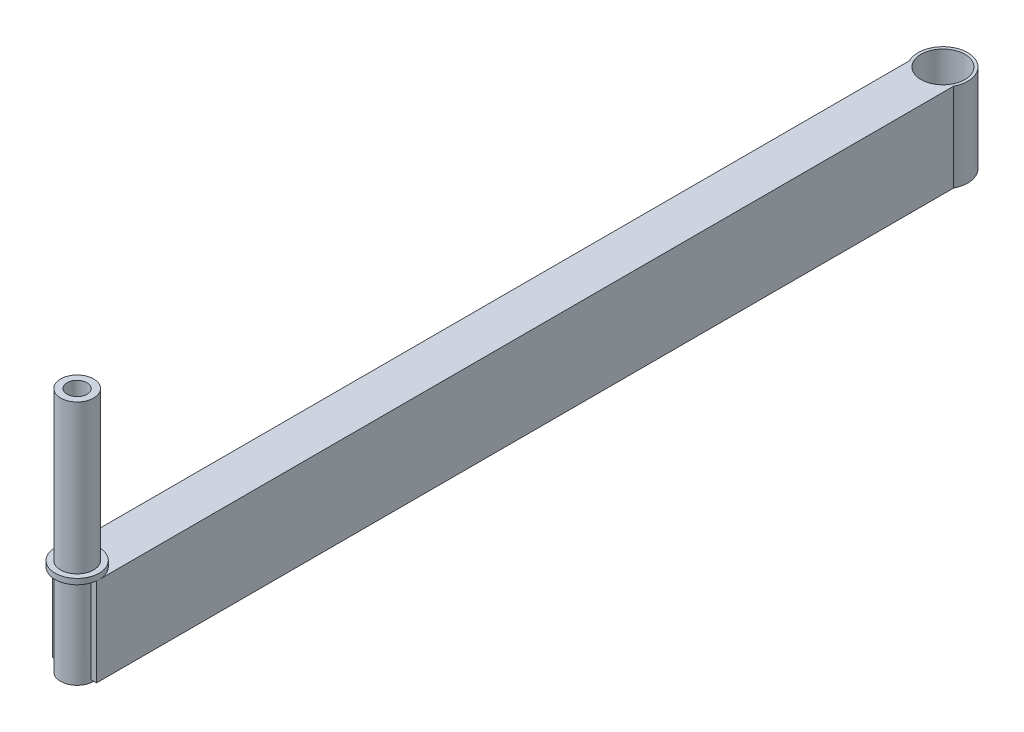
SolidWorks part; units mm, degrees
material "6061-T6 (SS)"
ref_plane "Front Plane" through (0, 0, 0) normal (0, 0, 1) x (1, 0, 0)
ref_plane "Top Plane" through (0, 0, 0) normal (0, 1, 0) x (1, 0, 0)
ref_plane "Right Plane" through (0, 0, 0) normal (1, 0, 0) x (0, 0, -1)
sketch "Sketch1" plane through (0, 0, 0) normal (0, 0, 1) x (1, 0, 0)
  line L0 (-11.1252, -23.8252) -> (-11.1252, 23.8252)
  line L1 (-12.7, -25.4) -> (12.7, -25.4)
  line L2 (-12.7, -25.4) -> (-12.7, 25.4)
  line L3 (-12.7, 25.4) -> (12.7, 25.4)
  line L4 (12.7, -25.4) -> (12.7, 25.4)
  line L5 (-12.7, -25.4) -> (12.7, 25.4) construction
  line L6 (-12.7, 25.4) -> (12.7, -25.4) construction
  line L7 (-11.1252, 23.8252) -> (11.1252, 23.8252)
  line L8 (11.1252, -23.8252) -> (11.1252, 23.8252)
  line L9 (-11.1252, -23.8252) -> (11.1252, -23.8252)
  point P0 (0, 0)
  dimension "D1" = 25.4
  dimension "D2" = 50.8
  dimension "D3" = 1.5748
extrude "Boss-Extrude1" add sketch "Sketch1" along normal blind 498.475
sketch "Sketch2" plane through (0, 25.4, 0) normal (0, 1, 0) x (1, 0, 0)
  line L0 (12.7, -498.475) -> (-12.7, -498.475) construction
  line L1 (12.7, -8.9803) -> (11.1125, -8.9803) construction
  line L2 (12.7, -498.475) -> (12.7, 0) construction
  circle A0 centre (0, 0) radius 14.2875
  circle A1 centre (0, -498.475) radius 9.525
  dimension "D1" = 28.575
  dimension "D2" = 19.05
  dimension "D3" = 1.5875
  dimension "D4" = 489.4947
extrude "Cut-Extrude1" cut sketch "Sketch2" against normal through all
sketch "Sketch3" plane through (0, 25.4, 0) normal (0, 1, 0) x (1, 0, 0)
  circle A0 centre (0, 0) radius 14.2875
  circle A1 centre (0, 0) radius 12.6365
  dimension "D1" = 28.575
  dimension "D2" = 1.651
extrude "Boss-Extrude2" add sketch "Sketch3" against normal blind 50.8
sketch "Sketch4" plane through (0, 25.4, 0) normal (0, 1, 0) x (1, 0, 0)
  circle A0 centre (0, -498.475) radius 9.525
  circle A1 centre (0, -498.475) radius 6.35
  dimension "D1" = 19.05
  dimension "D2" = 3.175
extrude "Boss-Extrude3" add sketch "Sketch4" along normal blind 88.9 and the other way blind 52.3875
sketch "Sketch5" plane through (0, 25.4, 0) normal (0, 1, 0) x (1, 0, 0)
  circle A0 centre (0, -498.475) radius 12.7
  circle A1 centre (0, -498.475) radius 9.525
  dimension "D1" = 25.4
  dimension "D2" = 19.05
extrude "Boss-Extrude4" add sketch "Sketch5" along normal blind 3.175
sketch "Sketch6" plane through (0, 114.3, 0) normal (0, 1, 0) x (1, 0, 0)
  circle A0 centre (0, -498.475) radius 6.35
extrude "Boss-Extrude5" add sketch "Sketch6" against normal blind 19.05
hole_wizard "Tap Drill for 1/2-20 Tap1" positions "Sketch8" profile "Sketch7" hole size "1/2-20" standard "ANSI Inch" end condition up to next
sketch "Sketch8" plane through (0, 114.3, 0) normal (0, 1, 0) x (1, 0, 0)
  point P0 (0, -498.475)
sketch "Sketch7" plane through (0, 114.3, 498.475) normal (1, 0, 0) x (0, 0, 1)
  line L0 (0, 0) -> (0, 19.05)
  line L1 (0, 19.05) -> (5.7544, 19.05)
  line L2 (5.7544, 19.05) -> (5.7544, 0)
  line L5 (5.7544, 0) -> (0, 0)
  line L11 (0, -6.35) -> (0, 107.95) construction
  dimension "Thru Hole Dia." = 11.5087
  dimension "Thru Hole Depth" = 19.05
sketch "Sketch9" plane through (12.7, 0, 0) normal (1, 0, 0) x (0, 0, -1)
  line L1 (-498.475, 25.4) -> (-499.999, 25.4)
  line L2 (-498.475, 25.4) -> (-498.475, -25.4)
  line L3 (-498.475, -25.4) -> (-499.999, -25.4)
  line L4 (-499.999, 25.4) -> (-499.999, -25.4)
  dimension "D1" = 50.8
  dimension "D2" = 1.524
extrude "Boss-Extrude6" add sketch "Sketch9" against normal up to surface (3.175 mm away) up to face at (0, -24.6126, 493.7125)
sketch "Sketch10" plane through (-12.7, 0, 0) normal (-1, 0, 0) x (0, 0, 1)
  line L1 (498.475, 25.4) -> (499.999, 25.4)
  line L2 (498.475, 25.4) -> (498.475, -25.4)
  line L3 (498.475, -25.4) -> (499.999, -25.4)
  line L4 (499.999, 25.4) -> (499.999, -25.4)
  dimension "D1" = 1.524
extrude "Boss-Extrude7" add sketch "Sketch10" against normal up to surface (3.2977 mm away) up to face at (-0.0153, 0, 496.2842)
sketch "Sketch11" plane through (0, 25.4, 0) normal (0, 1, 0) x (1, 0, 0)
  line L0 (0, 0) -> (0, -191.4003) construction
  line L1 (12.7, -498.475) -> (12.7, -6.5454) construction
  line L2 (12.7, -58.7375) -> (15.0812, -58.7375)
  line L3 (12.7, -58.7375) -> (12.7, -39.6875)
  line L4 (12.7, -39.6875) -> (15.0812, -39.6875)
  line L5 (15.0812, -58.7375) -> (15.0812, -39.6875)
  dimension "D1" = 39.6875
  dimension "D2" = 19.05
  dimension "D3" = 2.3813
extrude "Boss-Extrude8" [suppressed] add sketch "Sketch11" along normal blind 42.5577 and the other way blind 38.1
sketch "Sketch12" [suppressed] plane through (15.0812, 0, 0) normal (1, 0, 0) x (0, 0, -1)
  line L0 (-53.6575, 48.9077) -> (-44.7675, 48.9077) construction
  line L1 (-53.6575, 50.6857) -> (-44.7675, 50.6857)
  line L2 (-53.6575, 47.1297) -> (-44.7675, 47.1297)
  line L3 (-53.6575, 59.8297) -> (-44.7675, 59.8297) construction
  line L4 (-53.6575, 61.6077) -> (-44.7675, 61.6077)
  line L5 (-53.6575, 58.0517) -> (-44.7675, 58.0517)
  line L6 (-58.7375, -12.7) -> (-58.7375, 67.9577) construction
  line L7 (-39.6875, -12.7) -> (-39.6875, 67.9577) construction
  line L8 (-58.7375, 67.9577) -> (-39.6875, 67.9577) construction
  arc A0 (-53.6575, 50.6857) -> (-53.6575, 47.1297) centre (-53.6575, 48.9077) ccw
  arc A1 (-44.7675, 47.1297) -> (-44.7675, 50.6857) centre (-44.7675, 48.9077) ccw
  arc A2 (-53.6575, 61.6077) -> (-53.6575, 58.0517) centre (-53.6575, 59.8297) ccw
  arc A3 (-44.7675, 58.0517) -> (-44.7675, 61.6077) centre (-44.7675, 59.8297) ccw
  point P2 (-49.2125, 48.9077)
  point P7 (-49.2125, 59.8297)
  dimension "D1" = 1.778
  dimension "D2" = 5.08
  dimension "D3" = 5.08
  dimension "D4" = 19.05
  dimension "D5" = 10.922
  dimension "D6" = 5.08
extrude "Cut-Extrude2" [suppressed] cut sketch "Sketch12" against normal through all
chamfer "Chamfer1" [suppressed] distance 1.0668 angle 45
equation "\"mount\"=1.5625"
equation "\"D1@Sketch11\"=\"mount\""
